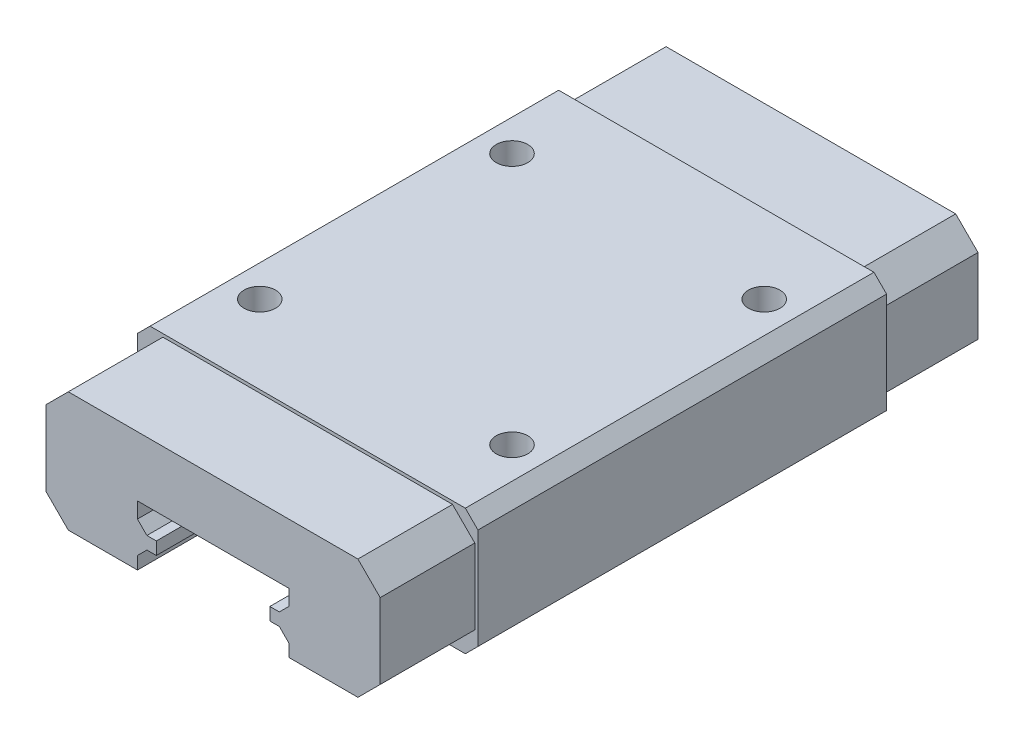
SolidWorks part; units mm, degrees
ref_plane "Front Plane" through (0, 0, 0) normal (0, 0, 1) x (1, 0, 0)
ref_plane "Top Plane" through (0, 0, 0) normal (0, 1, 0) x (1, 0, 0)
ref_plane "Right Plane" through (0, 0, 0) normal (1, 0, 0) x (0, 0, -1)
sketch "MGNR12R Rail" plane through (0, 0, 0) normal (0, 0, 1) x (1, 0, 0)
  line L0 (-6, -3) -> (6, -3) construction
  line L1 (6, -3) -> (6, 1.25) construction
  line L2 (6, 1.25) -> (5.25, 2) construction
  line L3 (5.25, 2) -> (4.5, 2) construction
  line L4 (4.5, 2) -> (4.5, 3) construction
  line L5 (4.5, 3) -> (5.25, 3) construction
  line L6 (5.25, 3) -> (6, 3.75) construction
  line L7 (6, 3.75) -> (6, 5) construction
  line L8 (6, 5) -> (-6, 5) construction
  line L9 (0, -3) -> (0, 5) construction
  line L10 (-6, 3.75) -> (-6, 5) construction
  line L11 (-5.25, 3) -> (-6, 3.75) construction
  line L12 (-4.5, 3) -> (-5.25, 3) construction
  line L13 (-4.5, 2) -> (-4.5, 3) construction
  line L14 (-5.25, 2) -> (-4.5, 2) construction
  line L15 (-6, 1.25) -> (-5.25, 2) construction
  line L16 (-6, -3) -> (-6, 1.25) construction
  point P20 (0.1263, -1.4969)
  point P21 (0, 0)
  point P22 (0, 0)
  dimension "D1" = 135
  dimension "D2" = 1
  dimension "D3" = 2
  dimension "D4" = 0.75
  dimension "D5" = 1.5
  dimension "D6" = 8
  dimension "D7" = 12
  dimension "D8" = 3
sketch "Sketch1" plane through (0, 0, 0) normal (0, 0, 1) x (1, 0, 0)
  line L0 (0, 0) -> (6.5, 0) construction
  line L1 (6.5, 0) -> (12.5, 0)
  line L2 (12.5, 0) -> (13.5, 1)
  line L3 (13.5, 1) -> (13.5, 9)
  line L4 (13.5, 9) -> (12.5, 10)
  line L5 (12.5, 10) -> (-12.5, 10)
  line L6 (0, 0) -> (0, 10) construction
  line L7 (6.5, 0) -> (6.5, 5.5)
  line L8 (6.5, 5.5) -> (-6.5, 5.5)
  line L9 (6, 3.75) -> (6, 5) construction
  line L10 (6, 5) -> (6.5, 5.5) construction
  line L11 (5.25, 3) -> (6, 3.75) construction
  line L12 (6, 1.25) -> (5.25, 2) construction
  line L13 (-6, 5) -> (-6.5, 5.5) construction
  line L14 (-6.5, 0) -> (-6.5, 5.5)
  line L15 (-13.5, 9) -> (-12.5, 10)
  line L16 (-13.5, 1) -> (-13.5, 9)
  line L17 (-12.5, 0) -> (-13.5, 1)
  line L18 (-6.5, 0) -> (-12.5, 0)
  circle A0 centre (6.5, 2.5) radius 1.2374 construction
  circle A1 centre (-6.5, 2.5) radius 1.2374 construction
  point P10 (0, 5.5)
  point P30 (25.6788, 0.8219)
  dimension "D1" = 135
  dimension "D2" = 10
  dimension "D3" = 3
  dimension "D4" = 0.5
  dimension "D5" = 45
  dimension "D6" = 27
  dimension "D7" = 1
extrude "Boss-Extrude1" add sketch "Sketch1" along normal mid plane 32.4
sketch "Sketch3" plane through (0, 0, 16.2) normal (0, 0, 1) x (1, 0, 0)
  line L0 (-6.5, 0) -> (-6.5, 5.5) construction
  line L1 (6.5, 5.5) -> (6.5, 0) construction
  circle A0 centre (-6.5, 2.5) radius 1.2374
  circle A1 centre (6.5, 2.5) radius 1.2374
  circle A2 centre (-6.5, 2.5) radius 1.2374 construction
  circle A3 centre (6.5, 2.5) radius 1.2374 construction
  point P8 (0, 0)
  point P12 (0, 0)
revolve "Revolve1" add sketch "Sketch3" angle 360 about axis through (-6.5, 0, 16.2) along (0, 1, 0) region at (-5.9748, 2.5, 16.2)
revolve "Revolve2" add sketch "Sketch3<3>" angle 360 about axis through (6.5, 0, 16.2) along (0, -1, 0) region at (5.9748, 2.5, 16.2)
sketch "Sketch3<3>" plane through (0, 0, 16.2) normal (0, 0, 1) x (1, 0, 0) same geometry as "Sketch3"
pattern_linear "LPattern1" count 10 spacing 3.5 along (0, 0, -1) of "Revolve1"
pattern_linear "LPattern2" count 10 spacing 3.5 along (0, 0, -1) of "Revolve2"
sketch "Sketch4" plane through (0, 0, 16.2) normal (0, 0, 1) x (1, 0, 0)
  line L0 (-6, 0.25) -> (-11.4822, 0.25)
  line L1 (-6, -3) -> (-6, 1.25) construction
  line L2 (-11.4822, 0.25) -> (-13.25, 2.0178)
  line L3 (-13.25, 2.0178) -> (-13.25, 7.9822)
  line L4 (-13.25, 7.9822) -> (-11.4822, 9.75)
  line L5 (-11.4822, 9.75) -> (11.4822, 9.75)
  line L6 (-6, 0.25) -> (-6, 1.25)
  line L7 (-6, 1.25) -> (-5.25, 2)
  line L8 (-5.25, 2) -> (-4.5, 2)
  line L9 (-4.5, 2) -> (-4.5, 3)
  line L10 (-4.5, 3) -> (-5.25, 3)
  line L11 (-5.25, 3) -> (-6, 3.75)
  line L12 (-6, 3.75) -> (-6, 5)
  line L13 (-6, 5) -> (6, 5)
  line L14 (0, 0) -> (0, 10) construction
  line L15 (0, 10) -> (0, 0) construction
  line L16 (12.5, 10) -> (-12.5, 10) construction
  line L17 (6, 3.75) -> (6, 5)
  line L18 (5.25, 3) -> (6, 3.75)
  line L19 (4.5, 3) -> (5.25, 3)
  line L20 (4.5, 2) -> (4.5, 3)
  line L21 (5.25, 2) -> (4.5, 2)
  line L22 (6, 1.25) -> (5.25, 2)
  line L23 (6, 0.25) -> (6, 1.25)
  line L24 (13.25, 7.9822) -> (11.4822, 9.75)
  line L25 (13.25, 2.0178) -> (13.25, 7.9822)
  line L26 (11.4822, 0.25) -> (13.25, 2.0178)
  line L27 (6, 0.25) -> (11.4822, 0.25)
  line L28 (-6.5, 0) -> (-12.5, 0) construction
  line L29 (-13.5, 1) -> (-13.5, 9) construction
  point P4 (0, 9.75)
  point P46 (-10.7276, 9.75)
  dimension "D1" = 0.25
  dimension "D2" = 0.25
  dimension "D3" = 0.25
  dimension "D4" = 135
  dimension "D5" = 2.5
extrude "Boss-Extrude3" add sketch "Sketch4" along normal blind 7.5 separate body
pattern_linear "LPattern3" count 2 spacing 39.9 along (0, 0, -1) of "Boss-Extrude3"
sketch "Sketch5" plane through (0, 10, 0) normal (0, 1, 0) x (1, 0, 0)
  line L1 (-10, -10) -> (10, -10) construction
  line L2 (-10, -10) -> (-10, 10) construction
  line L3 (-10, 10) -> (10, 10) construction
  line L4 (10, -10) -> (10, 10) construction
  line L5 (-10, -10) -> (10, 10) construction
  line L6 (-10, 10) -> (10, -10) construction
  point P0 (0, 0)
  point P6 (10, 10)
  point P8 (-10, 10)
  point P9 (-10, -10)
  point P10 (10, -10)
  dimension "D1" = 20
  dimension "D2" = 20
hole_wizard "Tap Drill for M3x0.5 Tap1" positions "3DSketch1" profile "Sketch6" hole size "M3x0.5" standard "ANSI Metric"
sketch3d "3DSketch1"
  point P0 (-10, 10, -10)
  point P3 (10, 10, -10)
  point P6 (-10, 10, 10)
  point P9 (10, 10, 10)
sketch "Sketch6" plane through (-10, 10, -10) normal (1, 0, 0) x (0, 0, 1)
  line L0 (0, 0) -> (0, 4.2511)
  line L1 (0, 4.2511) -> (1.25, 3.5)
  line L2 (1.25, 3.5) -> (1.25, 0)
  line L5 (1.25, 0) -> (0, 0)
  line L10 (0, 4.2511) -> (-1.25, 3.5) construction
  line L11 (0, -6.35) -> (0, 107.95) construction
  dimension "Hole Dia." = 2.5
  dimension "Hole Depth" = 3.5
  dimension "Drill Angle" = 118
